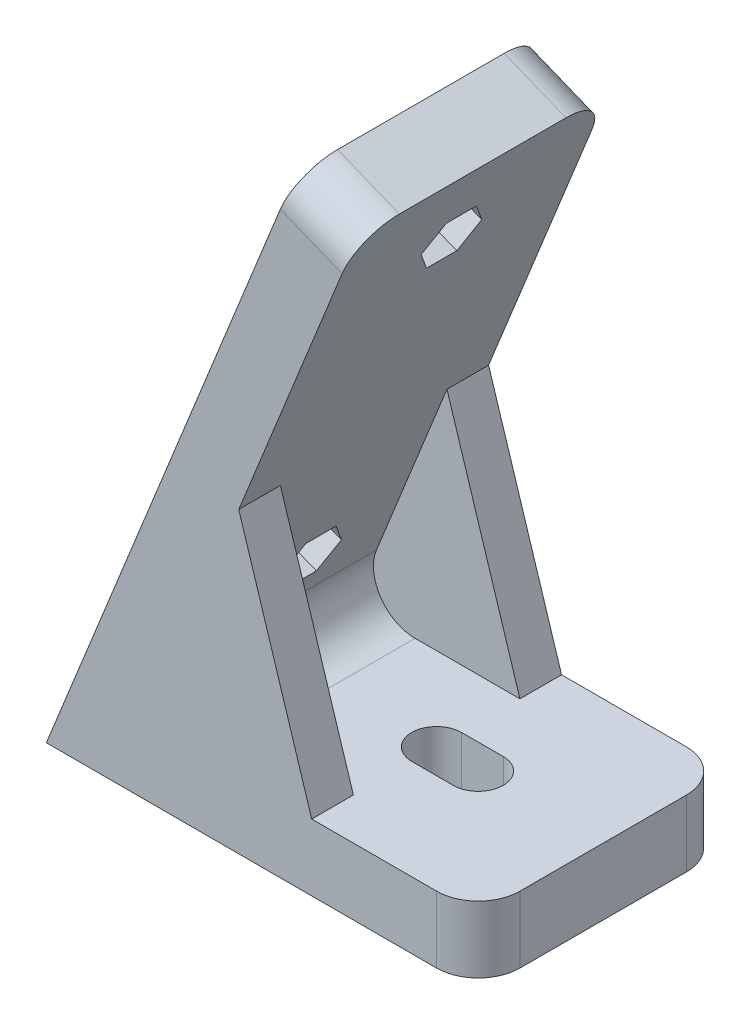
SolidWorks part; units mm, degrees
ref_plane "Front Plane" through (0, 0, 0) normal (0, 0, 1) x (1, 0, 0)
ref_plane "Top Plane" through (0, 0, 0) normal (0, 1, 0) x (1, 0, 0)
ref_plane "Right Plane" through (0, 0, 0) normal (1, 0, 0) x (0, 0, -1)
sketch "Sketch1" plane through (0, 0, 0) normal (0, 0, 1) x (1, 0, 0)
  line L0 (0, 0) -> (29.9685, 74.1747)
  line L4 (11.8605, 8) -> (37.386, 71.1779)
  line L5 (37.386, 71.1779) -> (29.9685, 74.1747)
  line L9 (0, 0) -> (51.8605, 0)
  line L13 (51.8605, 0) -> (51.8605, 8)
  line L15 (11.8605, 8) -> (51.8605, 8)
  dimension "D1" = 68
  dimension "D2" = 8
  dimension "D3" = 8
  dimension "D4" = 80
  dimension "D6" = 40
extrude "Boss-Extrude1" add sketch "Sketch1" along normal mid plane 30
sketch "Sketch2" plane through (0.3799, 8, 0) normal (0, 1, 0) x (1, 0, 0)
  line L0 (36.4805, 0) -> (31.4805, 0) construction
  line L1 (36.4805, -3) -> (31.4805, -3)
  line L2 (36.4805, 3) -> (31.4805, 3)
  line L4 (51.4805, -15) -> (51.4805, 15) construction
  arc A0 (36.4805, -3) -> (36.4805, 3) centre (36.4805, 0) ccw
  arc A1 (31.4805, 3) -> (31.4805, -3) centre (31.4805, 0) ccw
  point P3 (33.9805, 0)
  dimension "D3" = 3
  dimension "D1" = 5
  dimension "D2" = 15
extrude "Cut-Extrude1" cut sketch "Sketch2" against normal through all
sketch "Sketch3" plane through (7.4175, -2.9969, 0) normal (0.9272, -0.3746, 0) x (0, 0, -1)
sketch "Sketch4" plane through (0, 0, 15) normal (0, 0, 1) x (1, 0, 0)
  line L0 (23.0987, 35.8155) -> (31.8605, 8)
  line L3 (11.8605, 8) -> (37.386, 71.1779) construction
  line L5 (51.8605, 8) -> (11.8605, 8) construction
  dimension "D1" = 20
  dimension "D2" = 30
rib "Rib1" sketch "Sketch4" sketch "Sketch4" thickness 5 extrusion direction parallel to sketch draft on no parameters "D1"=5
mirror "Mirror1" about plane through (0, 0, 0) normal (0, 0, 1) of "Rib1"
sketch "Sketch6" plane through (7.4175, -2.9969, 0) normal (0.9272, -0.3746, 0) x (0, 0, -1)
  line L0 (-15, 80) -> (15, 80) construction
  point P0 (0, 70)
  point P2 (0, 25)
  point P9 (0, 80)
  dimension "D1" = 10
  dimension "D2" = 45
hole_wizard "M3 Clearance Hole1" positions "Sketch6" profile "Sketch7" hole size "M3" standard "ANSI Metric" end condition through all
sketch "Sketch7" plane through (33.6399, 61.906, 0) normal (0, 0, 1) x (0.3746, 0.9272, 0)
  line L0 (0, 0) -> (0, 35.7863)
  line L1 (0, 35.7863) -> (1.7, 35.7863)
  line L2 (1.7, 35.7863) -> (1.7, 0.025)
  line L3 (1.7, 0.025) -> (1.725, 0)
  line L5 (1.725, 0) -> (0, 0)
  line L6 (-1.7, 0.025) -> (-1.725, 0) construction
  line L11 (0, -6.35) -> (0, 107.95) construction
  dimension "Thru Hole Dia." = 3.4
  dimension "Thru Hole Depth" = 35.7863
  dimension "Near C'Sink Dia." = 3.45
  dimension "Near C'Sink Angle" = 90
sketch "Sketch8" plane through (7.4175, -2.9969, 0) normal (0.9272, -0.3746, 0) x (0, 0, -1)
  line L1 (3.6373, 70) -> (1.8187, 73.15)
  line L2 (1.8187, 73.15) -> (-1.8187, 73.15)
  line L3 (-1.8187, 73.15) -> (-3.6373, 70)
  line L4 (-3.6373, 70) -> (-1.8187, 66.85)
  line L5 (-1.8187, 66.85) -> (1.8187, 66.85)
  line L6 (1.8187, 66.85) -> (3.6373, 70)
  line L7 (3.6373, 25) -> (1.8187, 28.15)
  line L8 (1.8187, 28.15) -> (-1.8187, 28.15)
  line L9 (-1.8187, 28.15) -> (-3.6373, 25)
  line L10 (-3.6373, 25) -> (-1.8187, 21.85)
  line L11 (-1.8187, 21.85) -> (1.8187, 21.85)
  line L12 (1.8187, 21.85) -> (3.6373, 25)
  circle A0 centre (0, 70) radius 3.15 construction
  circle A1 centre (0, 25) radius 3.15 construction
  dimension "D1" = 6.3
extrude "Cut-Extrude2" cut sketch "Sketch8" against normal blind 3
fillet "Fillet1" radius 5 1 edges at (11.8605, 8, 0)
fillet "Fillet2" radius 5 4 edges at (33.6773, 72.6763, -15) (33.6773, 72.6763, 15) (51.8605, 4, -15) (51.8605, 4, 15)
ref_plane "Plane1" through (0, 0, 0) normal (0, 0, 1) x (1, 0, 0)
ref_plane "Plane2" through (34.3605, 0, 0) normal (1, 0, 0) x (0, 0, -1)
ref_axis "Axis1" through (34.3605, -0.4, 0) along (0, 1, 0)
